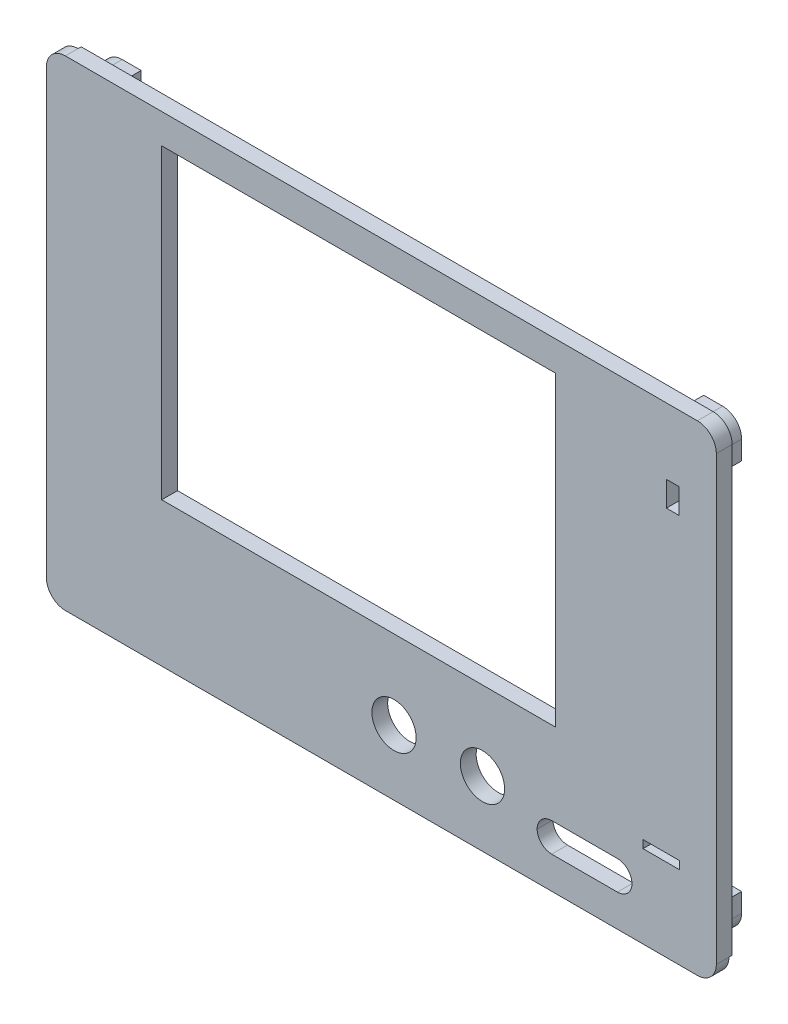
SolidWorks part; units mm, degrees
ref_plane "Ön Düzlem" through (0, 0, 0) normal (0, 0, 1) x (1, 0, 0)
ref_plane "Üst Düzlem" through (0, 0, 0) normal (0, 1, 0) x (1, 0, 0)
ref_plane "Sağ Düzlem" through (0, 0, 0) normal (1, 0, 0) x (0, 0, -1)
sketch "Çizim1" plane through (0, 0, 0) normal (0, 0, 1) x (1, 0, 0)
  line L1 (0, 0) -> (106, 0)
  line L2 (0, 0) -> (0, 76)
  line L3 (0, 76) -> (106, 76)
  line L4 (106, 0) -> (106, 76)
  circle A0 centre (55, 10.31) radius 3.5
  circle A1 centre (69, 10.31) radius 3.5
  point P6 (106, 76)
  point P11 (104.5223, 76)
  dimension "D7" = 7
  dimension "D8" = 7
  dimension "D9" = 10.31
  dimension "D1" = 76
  dimension "D2" = 106
  dimension "D5" = 55
  dimension "D6" = 14
  dimension "D10" = 10.31
extrude "Yükseklik-Ekstrüzyon2" add sketch "Çizim1" along normal blind 2.5
sketch "Çizim5" plane through (0, 0, 2.5) normal (0, 0, 1) x (1, 0, 0)
  line L0 (106, 76) -> (0, 76) construction
  line L1 (18.25, 71.3) -> (80.55, 71.3)
  line L2 (18.25, 71.3) -> (18.25, 22.8)
  line L3 (18.25, 22.8) -> (80.55, 22.8)
  line L4 (80.55, 71.3) -> (80.55, 22.8)
  line L5 (0, 76) -> (0, 0) construction
  dimension "D1" = 4.7
  dimension "D2" = 18.25
  dimension "D3" = 62.3
  dimension "D4" = 48.5
extrude "Kes-Ekstrüzyon1" cut sketch "Çizim5" against normal blind 2.5
sketch "Çizim7" plane through (0, 0, 0) normal (0, 0, -1) x (-1, 0, 0)
  line L0 (-103.5, 73.5) -> (-97.5, 73.5)
  line L5 (-101, 71) -> (-97.5, 71)
  line L6 (0, 0) -> (-106, 0) construction
  line L7 (-2.5, 2.5) -> (-8.5, 2.5)
  line L9 (-5, 5) -> (-8.5, 5)
  line L10 (-8.5, 2.5) -> (-8.5, 5)
  line L13 (-2.5, 8.5) -> (-5, 8.5)
  line L14 (-5, 5) -> (-5, 8.5)
  line L15 (-97.5, 73.5) -> (-97.5, 71)
  line L16 (-2.5, 8.5) -> (-2.5, 2.5)
  line L17 (0, 76) -> (0, 0) construction
  line L18 (0, 38) -> (-38.3157, 38) construction
  line L19 (-2.5, 67.5) -> (-2.5, 73.5)
  line L20 (-5, 71) -> (-5, 67.5)
  line L21 (-2.5, 67.5) -> (-5, 67.5)
  line L22 (-8.5, 73.5) -> (-8.5, 71)
  line L23 (-5, 71) -> (-8.5, 71)
  line L24 (-2.5, 73.5) -> (-8.5, 73.5)
  line L25 (-53, 0) -> (-53, 38) construction
  line L26 (-103.5, 8.5) -> (-103.5, 2.5)
  line L27 (-101, 5) -> (-101, 8.5)
  line L28 (-103.5, 8.5) -> (-101, 8.5)
  line L29 (-97.5, 2.5) -> (-97.5, 5)
  line L30 (-101, 5) -> (-97.5, 5)
  line L31 (-103.5, 2.5) -> (-97.5, 2.5)
  line L32 (-103.5, 67.5) -> (-101, 67.5)
  line L33 (-101, 71) -> (-101, 67.5)
  line L34 (-103.5, 67.5) -> (-103.5, 73.5)
  dimension "D1" = 2.5
  dimension "D2" = 6
  dimension "D3" = 2.5
  dimension "D4" = 2.5
  dimension "D5" = 6
  dimension "D6" = 2.5
extrude "Yükseklik-Ekstrüzyon6" add sketch "Çizim7" along normal blind 4
fillet "Radyus7" radius 3 4 edges at (2.5, 2.5, -2) (2.5, 73.5, -2) (103.5, 2.5, -2) (103.5, 73.5, -2)
fillet "Radyus15" radius 3 4 edges at (106, 0, 1.25) (106, 76, 1.25) (0, 76, 1.25) (0, 0, 1.25)
sketch "Çizim12" plane through (0, 0, 2.5) normal (0, 0, 1) x (1, 0, 0)
  line L0 (106, 3) -> (106, 73) construction
  line L1 (77.65, 9.69) -> (92.65, 9.69)
  line L2 (77.65, 9.69) -> (77.65, 5.09)
  line L3 (77.65, 5.09) -> (92.65, 5.09)
  line L4 (92.65, 9.69) -> (92.65, 5.09)
  line L5 (3, 0) -> (103, 0) construction
  line L6 (106, 3) -> (106, 73) construction
  line L7 (94.4, 14.32) -> (100.2, 14.32)
  line L8 (94.4, 14.32) -> (94.4, 13.07)
  line L9 (94.4, 13.07) -> (100.2, 13.07)
  line L10 (100.2, 14.32) -> (100.2, 13.07)
  line L11 (98.1, 65.53) -> (100.1, 65.53)
  line L12 (98.1, 65.53) -> (98.1, 61.58)
  line L13 (98.1, 61.58) -> (100.1, 61.58)
  line L14 (100.1, 65.53) -> (100.1, 61.58)
  line L15 (103, 76) -> (3, 76) construction
  dimension "D1" = 13.35
  dimension "D2" = 15
  dimension "D3" = 4.6
  dimension "D4" = 5.09
  dimension "D5" = 1.25
  dimension "D6" = 5.8
  dimension "D7" = 13.07
  dimension "D8" = 5.8
  dimension "D9" = 3.95
  dimension "D10" = 2
  dimension "D11" = 10.47
  dimension "D12" = 5.9
extrude "Kes-Ekstrüzyon3" cut sketch "Çizim12" against normal blind 4
fillet "Radyus16" radius 2.3 4 edges at (92.65, 5.09, 1.25) (92.65, 9.69, 1.25) (77.65, 9.69, 1.25) (77.65, 5.09, 1.25)
sketch "Çizim14" plane through (0, 0, 0) normal (0, 0, -1) x (-1, 0, 0)
  line L2 (-106, 3) -> (-105, 3)
  line L3 (-103, 1) -> (-103, 0)
  line L4 (-3, 1) -> (-3, 0)
  line L5 (0, 3) -> (-1, 3)
  line L6 (-3, 76) -> (-3, 75)
  line L7 (-1, 73) -> (0, 73)
  arc A2 (0, 73) -> (-3, 76) centre (-3, 73) ccw construction
  arc A3 (-3, 0) -> (0, 3) centre (-3, 3) ccw construction
  arc A4 (-106, 3) -> (-103, 0) centre (-103, 3) ccw construction
  arc A5 (0, 73) -> (-3, 76) centre (-3, 73) ccw
  arc A6 (-3, 0) -> (0, 3) centre (-3, 3) ccw
  arc A7 (-106, 3) -> (-103, 0) centre (-103, 3) ccw
  arc A9 (-1, 73) -> (-3, 75) centre (-3, 73) ccw
  arc A10 (-3, 1) -> (-1, 3) centre (-3, 3) ccw
  arc A11 (-105, 3) -> (-103, 1) centre (-103, 3) ccw
  point P0 (-1.5858, 74.4142)
  dimension "D1" = 2
extrude "Kes-Ekstrüzyon5" cut sketch "Çizim14" against normal blind 0.5
fillet "Radyus17" radius 1.5 16 edges at (3.75, 67.5, 0) (5, 69.25, 0) (6.75, 71, 0) (8.5, 72.25, 0) (5, 6.75, 0) (3.75, 8.5, 0) (6.75, 5, 0) (8.5, 3.75, 0) (97.5, 3.75, 0) (99.25, 5, 0) (101, 6.75, 0) (102.25, 8.5, 0) (97.5, 72.25, 0) (102.25, 67.5, 0) (99.25, 71, 0) (101, 69.25, 0)
